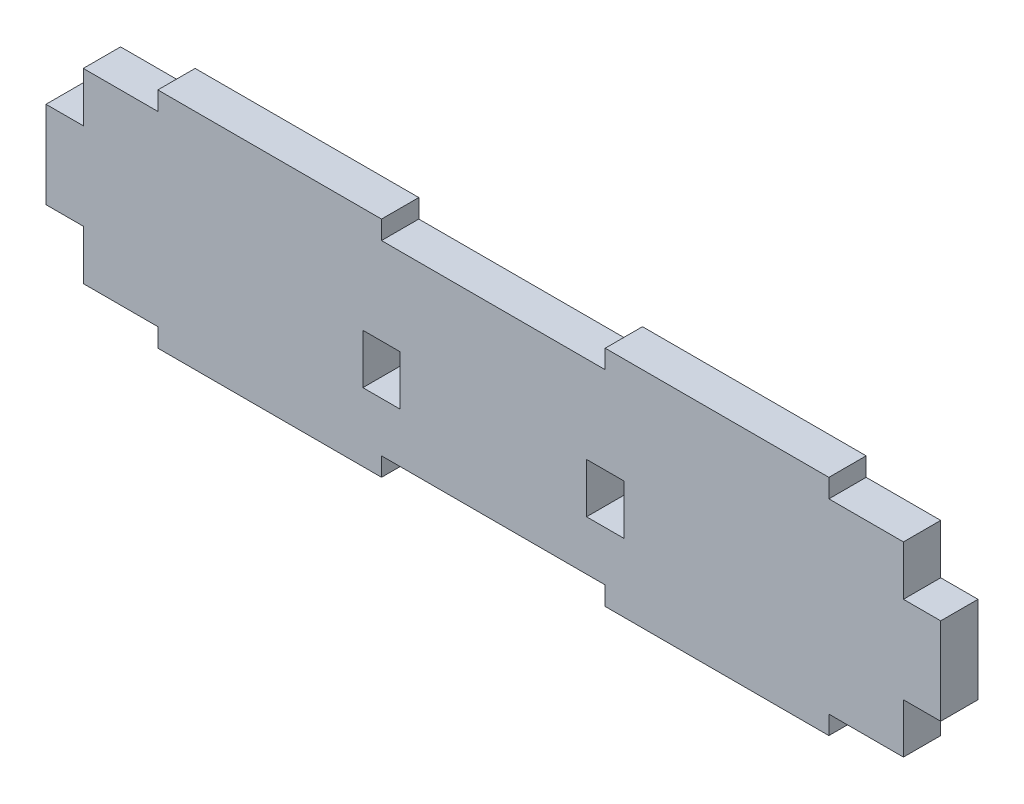
SolidWorks part; units mm, degrees
ref_plane "Front Plane" through (0, 0, 0) normal (0, 0, 1) x (1, 0, 0)
ref_plane "Top Plane" through (0, 0, 0) normal (0, 1, 0) x (1, 0, 0)
ref_plane "Right Plane" through (0, 0, 0) normal (1, 0, 0) x (0, 0, -1)
sketch "Sketch1" plane through (0, 0, 0) normal (0, 0, 1) x (1, 0, 0)
  line L1 (-152.4, -31.75) -> (152.4, -31.75)
  line L2 (-152.4, -31.75) -> (-152.4, 31.75)
  line L3 (-152.4, 31.75) -> (152.4, 31.75)
  line L4 (152.4, -31.75) -> (152.4, 31.75)
  line L5 (-152.4, -31.75) -> (152.4, 31.75) construction
  line L6 (-152.4, 31.75) -> (152.4, -31.75) construction
  point P0 (0, 0)
  dimension "D1" = 304.8
  dimension "D2" = 63.5
extrude "Boss-Extrude1" add sketch "Sketch1" along normal blind 12.7 contours L1 L3 region at (0, 0, 0)
sketch "Sketch2" plane through (0, 0, 12.7) normal (0, 0, 1) x (1, 0, 0)
  line L0 (-152.4, -31.75) -> (152.4, -31.75) construction
  line L1 (-38.1, -31.75) -> (-114.3, -31.75)
  line L2 (-38.1, -31.75) -> (-38.1, -38.1)
  line L3 (-38.1, -38.1) -> (-114.3, -38.1)
  line L4 (-114.3, -31.75) -> (-114.3, -38.1)
  line L5 (0, -55) -> (0, 55) construction
  line L6 (38.1, -38.1) -> (114.3, -38.1)
  line L7 (114.3, -31.75) -> (114.3, -38.1)
  line L8 (38.1, -31.75) -> (114.3, -31.75)
  line L9 (38.1, -31.75) -> (38.1, -38.1)
  line L10 (55, 0) -> (-55, 0) construction
  line L11 (38.1, 31.75) -> (38.1, 38.1)
  line L12 (38.1, 31.75) -> (114.3, 31.75)
  line L13 (114.3, 31.75) -> (114.3, 38.1)
  line L14 (38.1, 38.1) -> (114.3, 38.1)
  line L15 (-38.1, 38.1) -> (-114.3, 38.1)
  line L16 (-114.3, 31.75) -> (-114.3, 38.1)
  line L17 (-38.1, 31.75) -> (-114.3, 31.75)
  line L18 (-38.1, 31.75) -> (-38.1, 38.1)
  point P12 (-38.1, -34.925)
  dimension "D1" = 76.2
  dimension "D2" = 6.35
  dimension "D3" = 76.2
extrude "Boss-Extrude2" add sketch "Sketch2" against normal blind 12.7
sketch "Sketch3" plane through (0, 0, 12.7) normal (0, 0, 1) x (1, 0, 0)
  line L0 (55, 0) -> (-55, 0) construction
  line L1 (-152.4, -31.75) -> (-139.7, -31.75)
  line L2 (-152.4, -31.75) -> (-152.4, -14.8167)
  line L3 (-152.4, -14.8167) -> (-139.7, -14.8167)
  line L4 (-139.7, -31.75) -> (-139.7, -14.8167)
  line L5 (152.4, -31.75) -> (152.4, 31.75) construction
  line L6 (-152.4, 14.8167) -> (-139.7, 14.8167)
  line L7 (-139.7, 31.75) -> (-139.7, 14.8167)
  line L8 (-152.4, 31.75) -> (-139.7, 31.75)
  line L9 (-152.4, 31.75) -> (-152.4, 14.8167)
  line L10 (0, -55) -> (0, 55) construction
  line L11 (152.4, 31.75) -> (152.4, 14.8167)
  line L12 (152.4, 31.75) -> (139.7, 31.75)
  line L13 (139.7, 31.75) -> (139.7, 14.8167)
  line L14 (152.4, 14.8167) -> (139.7, 14.8167)
  line L15 (152.4, -14.8167) -> (139.7, -14.8167)
  line L16 (139.7, -31.75) -> (139.7, -14.8167)
  line L17 (152.4, -31.75) -> (139.7, -31.75)
  line L18 (152.4, -31.75) -> (152.4, -14.8167)
  line L19 (31.75, 2.1167) -> (44.45, 2.1167)
  line L20 (31.75, 2.1167) -> (31.75, -14.8167)
  line L21 (31.75, -14.8167) -> (44.45, -14.8167)
  line L22 (44.45, 2.1167) -> (44.45, -14.8167)
  line L23 (-38.1, -31.75) -> (38.1, -31.75) construction
  line L24 (-31.75, -14.8167) -> (-44.45, -14.8167)
  line L25 (-44.45, 2.1167) -> (-44.45, -14.8167)
  line L26 (-31.75, 2.1167) -> (-44.45, 2.1167)
  line L27 (-31.75, 2.1167) -> (-31.75, -14.8167)
  dimension "D1" = 16.9333
  dimension "D2" = 12.7
  dimension "D3" = 107.95
  dimension "D4" = 12.7
  dimension "D5" = 16.9333
  dimension "D6" = 16.9333
extrude "Cut-Extrude1" cut sketch "Sketch3" against normal through all
